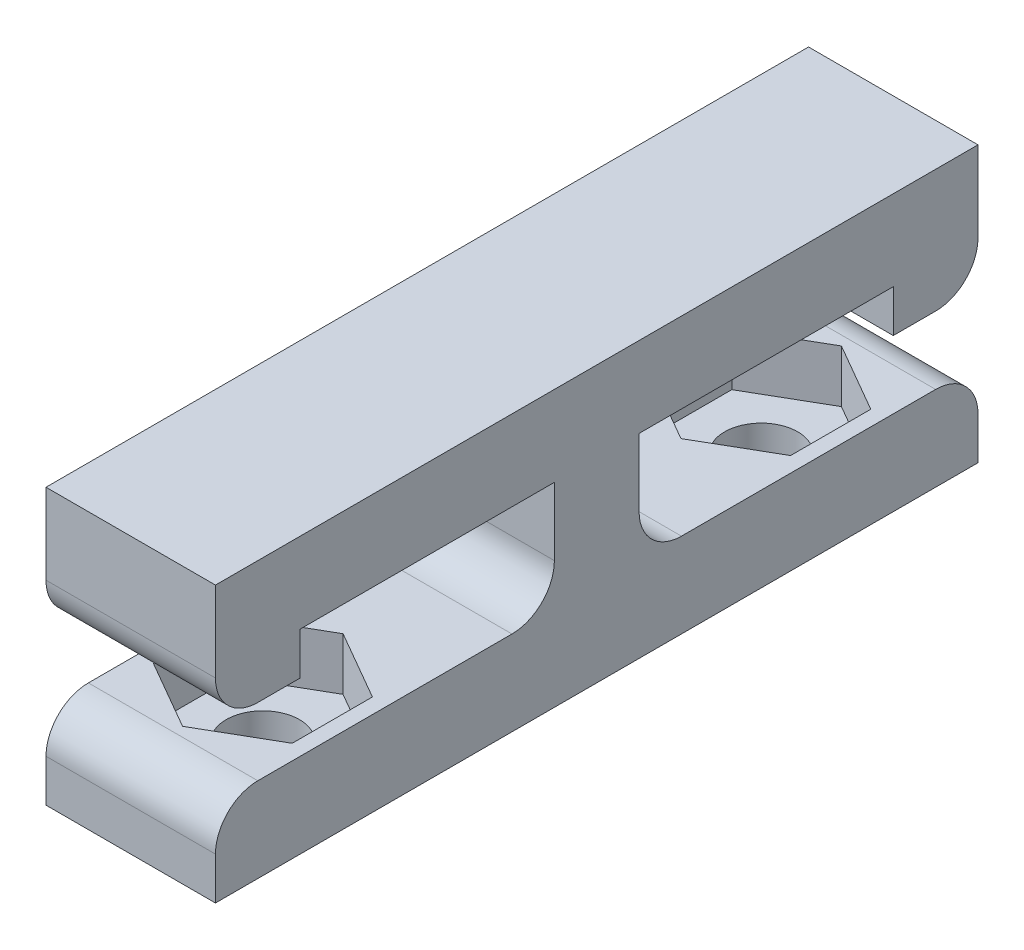
SolidWorks part; units mm, degrees
ref_plane "Front Plane" through (0, 0, 0) normal (0, 0, 1) x (1, 0, 0)
ref_plane "Top Plane" through (0, 0, 0) normal (0, 1, 0) x (1, 0, 0)
ref_plane "Right Plane" through (0, 0, 0) normal (1, 0, 0) x (0, 0, -1)
sketch "Sketch1" plane through (0, 0, 0) normal (0, 1, 0) x (1, 0, 0)
  line L0 (5, 45) -> (5, 0) construction
  line L1 (0, 0) -> (10, 0)
  line L2 (0, 0) -> (0, 45)
  line L3 (0, 45) -> (10, 45)
  line L4 (10, 0) -> (10, 45)
  line L5 (0, 22.5) -> (10, 22.5) construction
  circle A0 centre (5, 37.205) radius 2.16
  circle A1 centre (5, 7.795) radius 2.16
  dimension "D3" = 29.41
  dimension "D4" = 14.705
  dimension "D5" = 4.32
  dimension "D6" = 4.32
  dimension "D1" = 10
  dimension "D2" = 45
extrude "Boss-Extrude1" add sketch "Sketch1" along normal blind 5
sketch "Sketch2" plane through (0, 5, 0) normal (0, 1, 0) x (1, 0, 0)
  line L1 (5, 32.4707) -> (9.1, 34.8379)
  line L2 (9.1, 34.8379) -> (9.1, 39.5721)
  line L3 (9.1, 39.5721) -> (5, 41.9393)
  line L4 (5, 41.9393) -> (0.9, 39.5721)
  line L5 (0.9, 39.5721) -> (0.9, 34.8379)
  line L6 (0.9, 34.8379) -> (5, 32.4707)
  line L7 (5, 12.5293) -> (0.9, 10.1621)
  line L8 (0.9, 10.1621) -> (0.9, 5.4279)
  line L9 (0.9, 5.4279) -> (5, 3.0607)
  line L10 (5, 3.0607) -> (9.1, 5.4279)
  line L11 (9.1, 5.4279) -> (9.1, 10.1621)
  line L12 (9.1, 10.1621) -> (5, 12.5293)
  circle A0 centre (5, 37.205) radius 4.1 construction
  circle A1 centre (5, 7.795) radius 4.1 construction
  dimension "D1" = 8.2
  dimension "D2" = 8.2
extrude "Cut-Extrude1" cut sketch "Sketch2" against normal blind 3.1
sketch "Sketch3" plane through (0, 0, 0) normal (-1, 0, 0) x (0, 0, 1)
  line L0 (-22.5, 5) -> (-22.5, 0) construction
  line L1 (-45, 5) -> (0, 5) construction
  line L2 (-45, 0) -> (0, 0) construction
  line L3 (-25, 5) -> (-25, 11.5)
  line L4 (-25, 11.5) -> (-40, 11.5)
  line L5 (-40, 11.5) -> (-40, 9)
  line L6 (-40, 9) -> (-45, 9)
  line L7 (-45, 9) -> (-45, 16.25)
  line L8 (-45, 16.25) -> (0, 16.25)
  line L9 (-20, 5) -> (-20, 11.5)
  line L10 (0, 9) -> (0, 16.25)
  line L11 (-5, 9) -> (0, 9)
  line L12 (-5, 11.5) -> (-5, 9)
  line L13 (-20, 11.5) -> (-5, 11.5)
  line L14 (-25, 5) -> (-20, 5)
  point P16 (-22.5, 16.25)
  dimension "D1" = 6.5
  dimension "D2" = 15
  dimension "D3" = 5
  dimension "D4" = 7.25
  dimension "D5" = 5
  dimension "D6" = 2.5
extrude "Boss-Extrude2" add sketch "Sketch3" against normal through all
fillet "Fillet1" radius 2.5 6 edges at (5, 5, -45) (5, 5, 0) (5, 9, 0) (5, 9, -45) (5, 5, -20) (5, 5, -25)
